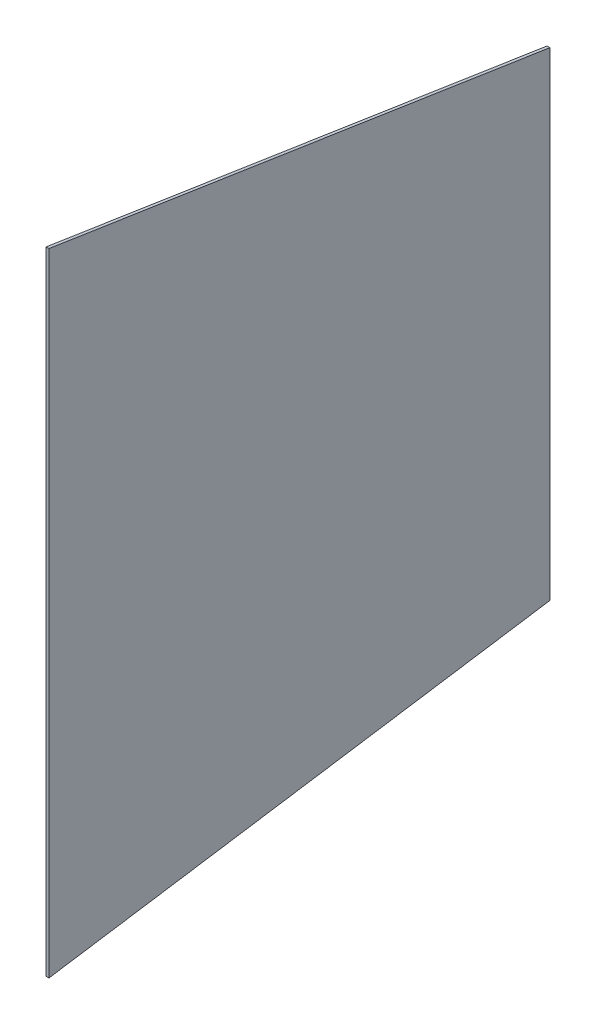
SolidWorks part; units mm, degrees
material "AISI 4130 Steel, annealed at 865C"
ref_plane "Plane1" through (0, 0, 0) normal (0, 0, 1) x (1, 0, 0)
ref_plane "Plane2" through (0, 0, 0) normal (0, 1, 0) x (1, 0, 0)
ref_plane "Plane3" through (0, 0, 0) normal (1, 0, 0) x (0, 0, -1)
ref_axis "Axis1" through (-83.9706, 0, 0) along (1, 0, 0)
ref_axis "Axis2" through (0, 0, -88.99) along (0, 0, 1)
ref_axis "Axis3" through (0, 55, 0) along (0, -1, 0)
sketch "Sketch1" plane through (0, 0, 0) normal (1, 0, 0) x (0, 0, -1)
  line L0 (166.6875, 174.1742) -> (166.6875, -174.1742) construction
  line L1 (166.6875, -174.1742) -> (442.9125, -131.9865) construction
  line L2 (442.9125, -131.9865) -> (442.9125, 131.9865) construction
  line L3 (442.9125, 131.9865) -> (166.6875, 174.1742) construction
  line L4 (166.6875, 174.1742) -> (166.6875, -174.1742)
  line L5 (166.6875, -174.1742) -> (442.9125, -131.9865)
  line L6 (442.9125, -131.9865) -> (442.9125, 131.9865)
  line L7 (442.9125, 131.9865) -> (166.6875, 174.1742)
ref_plane "Plane4" through (14.2875, 0, 0) normal (1, 0, 0) x (0, 0, -1)
sketch "Sketch2" plane through (14.2875, 0, 0) normal (1, 0, 0) x (0, 0, -1)
  line L4 (166.6875, 174.1742) -> (166.6875, -174.1742)
  line L5 (166.6875, -174.1742) -> (442.9125, -131.9865)
  line L6 (442.9125, -131.9865) -> (442.9125, 131.9865)
  line L7 (442.9125, 131.9865) -> (166.6875, 174.1742)
  line L8 (166.6875, 174.1742) -> (166.6875, -174.1742)
  line L9 (166.6875, -174.1742) -> (442.9125, -131.9865)
  line L10 (442.9125, -131.9865) -> (442.9125, 131.9865)
  line L11 (442.9125, 131.9865) -> (166.6875, 174.1742)
  dimension "D1" = 0
extrude "Boss-Extrude1" add sketch "Sketch2" along normal blind 1.5875
